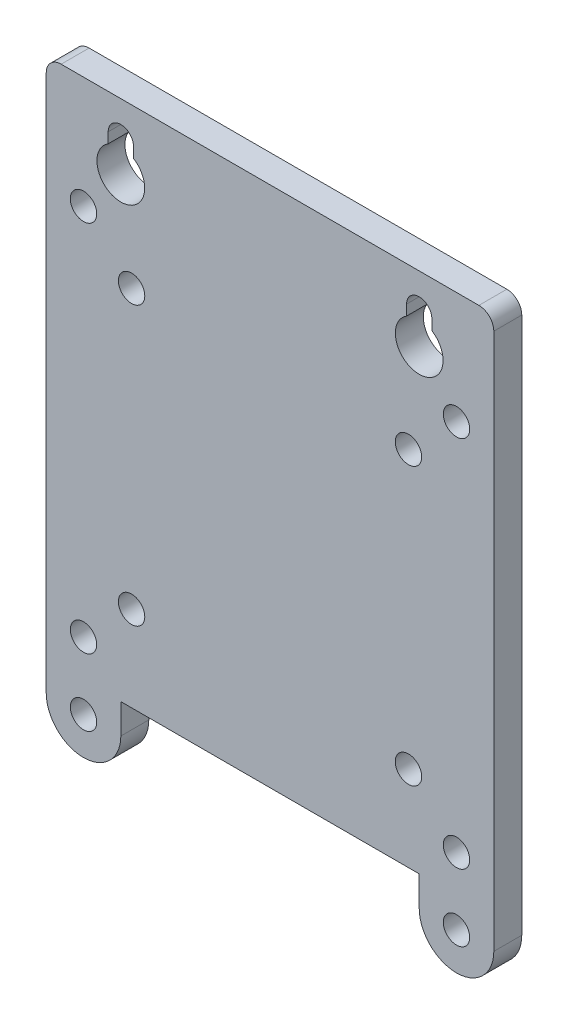
SolidWorks part; units mm, degrees
ref_plane "Front Plane" through (0, 0, 0) normal (0, 0, 1) x (1, 0, 0)
ref_plane "Top Plane" through (0, 0, 0) normal (0, 1, 0) x (1, 0, 0)
ref_plane "Right Plane" through (0, 0, 0) normal (1, 0, 0) x (0, 0, -1)
sketch "Sketch1" plane through (0, 0, 0) normal (0, 0, 1) x (1, 0, 0)
  line L1 (38.1, -38.1) -> (-38.1, -38.1)
  line L2 (38.1, -38.1) -> (38.1, 50.8)
  line L3 (38.1, 50.8) -> (-38.1, 50.8)
  line L4 (-38.1, -38.1) -> (-38.1, 50.8)
  line L5 (38.1, -38.1) -> (-38.1, 50.8) construction
  line L6 (38.1, 50.8) -> (-38.1, -38.1) construction
  point P0 (0, 6.35)
  dimension "D1" = 88.9
  dimension "D2" = 76.2
  dimension "D3" = 6.35
extrude "Boss-Extrude1" add sketch "Sketch1" along normal blind 4.7625
hole_wizard "#8 Clearance Hole1" positions "Sketch3" profile "Sketch2" hole size "#8" standard "ANSI Inch" end condition through all
sketch "Sketch3" plane through (0, 0, 4.7625) normal (0, 0, 1) x (1, 0, 0)
  point P0 (23.57, 23.57)
  point P3 (-23.57, 23.755)
  point P17 (23.57, -23.57)
  point P20 (-23.57, -23.57)
sketch "Sketch2" plane through (23.57, 23.57, 4.7625) normal (1, 0, 0) x (0, -1, 0)
  line L0 (0, 0) -> (0, 4.7625)
  line L1 (0, 4.7625) -> (2.2479, 4.7625)
  line L2 (2.2479, 4.7625) -> (2.2479, 0)
  line L5 (2.2479, 0) -> (0, 0)
  line L11 (0, -6.35) -> (0, 107.95) construction
  dimension "Thru Hole Dia." = 4.4958
  dimension "Thru Hole Depth" = 4.7625
fillet "Fillet1" radius 2.54 4 edges at (38.1, -38.1, 2.3813) (-38.1, -38.1, 2.3813) (-38.1, 50.8, 2.3813) (38.1, 50.8, 2.3813)
hole_wizard "#8 Clearance Slot1" positions "Sketch5" profile "Sketch4" size "#8" standard "ANSI Inch" slot yes end condition through all
sketch "Sketch5" plane through (0, 0, 0) normal (0, 0, -1) x (-1, 0, 0)
  line L0 (-25.4, 46.99) -> (-25.4, 37.465) construction
  line L1 (-12.7, 42.2275) -> (-38.1, 42.2275) construction
  line L3 (-38.1, -35.56) -> (-38.1, 48.26) construction
  line L5 (-35.56, 50.8) -> (35.56, 50.8) construction
  line L19 (0, 50.8) -> (0, -38.1) construction
  line L20 (35.56, -38.1) -> (-35.56, -38.1) construction
  line L22 (12.7, 42.2275) -> (38.1, 42.2275) construction
  line L23 (25.4, 46.99) -> (25.4, 37.465) construction
  line L24 (-38.1, -35.56) -> (-38.1, 48.26) construction
  point P0 (-25.4, 42.2275)
  point P61 (25.4, 42.2275)
  dimension "D1" = 9.525
  dimension "D2" = 3.81
  dimension "D3" = 12.7
sketch "Sketch4" plane through (25.4, 42.2275, 0) normal (1, 0, 0) x (0, 1, 0)
  line L0 (0, 0) -> (0, 4.7625)
  line L1 (0, 4.7625) -> (2.1526, 4.7625)
  line L2 (2.1526, 4.7625) -> (2.1526, 0)
  line L5 (2.1526, 0) -> (0, 0)
  line L11 (0, -6.35) -> (0, 107.95) construction
  dimension "Thru Hole Dia." = 4.3053
  dimension "Thru Hole Depth" = 4.7625
sketch "Sketch6" plane through (0, 0, 0) normal (0, 0, -1) x (-1, 0, 0)
  line L0 (0, 50.8) -> (0, -38.1) construction
  line L1 (-35.56, 50.8) -> (35.56, 50.8) construction
  line L2 (35.56, -38.1) -> (-35.56, -38.1) construction
  circle A0 centre (-25.4, 39.6176) radius 4.064
  circle A3 centre (25.4, 39.6177) radius 4.064
  dimension "D1" = 8.128
extrude "Cut-Extrude1" cut sketch "Sketch6" against normal through all
hole_wizard "#8 Clearance Hole2" positions "Sketch8" profile "Sketch7" hole size "#8" standard "ANSI Inch" end condition through all
sketch "Sketch8" plane through (0, 0, 0) normal (0, 0, -1) x (-1, 0, 0)
  line L8 (0, 0.7181) -> (23.57, 23.755) construction
  line L12 (0, 0.7181) -> (0, -38.1) construction
  line L13 (35.56, -38.1) -> (-35.56, -38.1) construction
  point P115 (31.75, 31.75)
  point P130 (31.75, -31.75)
  point P131 (-31.75, -31.75)
  point P132 (-31.75, 31.75)
  dimension "D1" = 31.75
  dimension "D2" = 63.5
  dimension "D3" = 6.35
sketch "Sketch7" plane through (-31.75, 31.75, 0) normal (1, 0, 0) x (0, 1, 0)
  line L0 (0, 0) -> (0, 4.7625)
  line L1 (0, 4.7625) -> (2.2479, 4.7625)
  line L2 (2.2479, 4.7625) -> (2.2479, 0)
  line L5 (2.2479, 0) -> (0, 0)
  line L11 (0, -6.35) -> (0, 107.95) construction
  dimension "Thru Hole Dia." = 4.4958
  dimension "Thru Hole Depth" = 4.7625
sketch "Sketch9" plane through (0, 0, 4.7625) normal (0, 0, 1) x (1, 0, 0)
  line L0 (-31.75, -31.75) -> (-31.75, -47.6777) construction
  line L2 (-35.56, -38.1) -> (35.56, -38.1) construction
  line L3 (-38.1, -43.18) -> (-25.4, -43.18) construction
  line L4 (-38.1, -43.18) -> (-38.1, -35.56)
  line L5 (-38.1, -35.56) -> (-25.4, -35.56)
  line L6 (-25.4, -35.56) -> (-25.4, -43.18)
  line L7 (0, 0) -> (0, -38.1) construction
  line L8 (38.1, -43.18) -> (25.4, -43.18) construction
  line L9 (31.75, -31.75) -> (31.75, -47.6777) construction
  line L10 (25.4, -35.56) -> (25.4, -43.18)
  line L11 (38.1, -35.56) -> (25.4, -35.56)
  line L12 (38.1, -43.18) -> (38.1, -35.56)
  circle A0 centre (-31.75, -43.18) radius 2.2479
  arc A2 (-38.1, -43.18) -> (-25.4, -43.18) centre (-31.75, -43.18) ccw
  arc A3 (38.1, -43.18) -> (25.4, -43.18) centre (31.75, -43.18) cw
  circle A4 centre (31.75, -43.18) radius 2.2479
  dimension "D1" = 4.4958
  dimension "D3" = 5.08
extrude "Boss-Extrude2" add sketch "Sketch9" against normal through all
